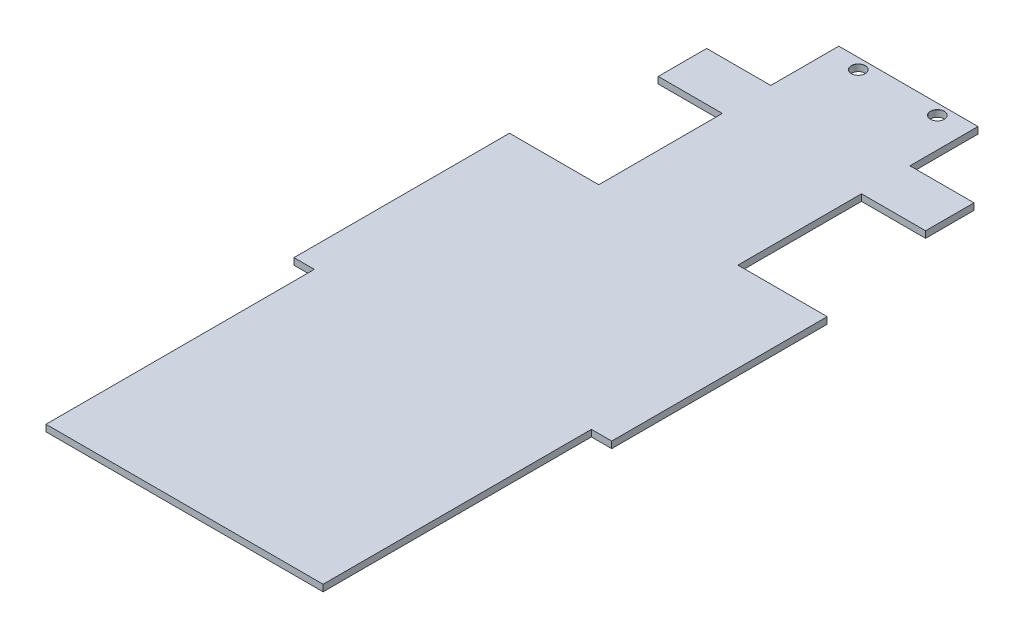
SolidWorks part; units mm, degrees
ref_plane "Plan de face" through (0, 0, 0) normal (0, 0, 1) x (1, 0, 0)
ref_plane "Plan de dessus" through (0, 0, 0) normal (0, 1, 0) x (1, 0, 0)
ref_plane "Plan de droite" through (0, 0, 0) normal (1, 0, 0) x (0, 0, -1)
sketch "Esquisse1" plane through (0, 0, 0) normal (0, 1, 0) x (1, 0, 0)
  line L3 (45, -30.525) -> (45, 30.525)
  line L5 (-45, -30.525) -> (-45, 30.525)
  line L10 (-19.715, 79.245) -> (-19.715, 98.525)
  line L12 (19.715, 98.525) -> (-19.715, 98.525)
  line L15 (-19.715, 65.525) -> (-37.865, 65.525)
  line L16 (-19.715, 79.245) -> (-37.865, 79.245)
  line L17 (-37.865, 79.245) -> (-37.865, 65.525)
  line L18 (19.715, 79.245) -> (37.865, 79.245)
  line L19 (37.865, 79.245) -> (37.865, 65.525)
  line L20 (37.865, 65.525) -> (19.715, 65.525)
  line L21 (-19.715, 65.525) -> (-19.715, 30.525)
  line L22 (19.715, 98.525) -> (19.715, 79.245)
  line L23 (-39.25, -106.525) -> (39.25, -106.525)
  line L24 (-39.25, -106.525) -> (-39.25, -30.525)
  line L25 (39.25, -106.525) -> (39.25, -30.525)
  line L26 (19.715, 65.525) -> (19.715, 30.525)
  line L27 (-45, 30.525) -> (-19.715, 30.525)
  line L28 (19.715, 30.525) -> (45, 30.525)
  line L29 (-45, -30.525) -> (-39.25, -30.525)
  line L30 (39.25, -30.525) -> (45, -30.525)
  dimension "D1" = 39.43
  dimension "D2" = 35
  dimension "D3" = 13.72
  dimension "D4" = 18.15
extrude "Boss.-Extru.6" add sketch "Esquisse1" along normal blind 1.87 contours L5 L27 L21 L15 L17 L16 L10 L12 L22 L18 L19 L20 L26 L28 L3 L30 L25 L23 L24 L29
sketch "Esquisse5" plane through (0, 1.87, 0) normal (0, 1, 0) x (1, 0, 0)
  circle A0 centre (-11.195, 95.525) radius 1.95
  circle A1 centre (11.195, 95.525) radius 1.95
hole_wizard "Dégagement M3.52" positions "Esquisse3D1" profile "Esquisse6" hole size "M3.5" standard "Ansi Metric" end condition through all
sketch3d "Esquisse3D1"
  point P0 (-11.195, 1.87, -95.525)
  point P3 (11.195, 1.87, -95.525)
sketch "Esquisse6" plane through (-11.195, 1.87, -95.525) normal (1, 0, 0) x (0, 0, 1)
  line L0 (0, 0) -> (0, 1.87)
  line L1 (0, 1.87) -> (1.95, 1.87)
  line L2 (1.95, 1.87) -> (1.95, 0.025)
  line L3 (1.95, 0.025) -> (1.975, 0)
  line L5 (1.975, 0) -> (0, 0)
  line L6 (-1.95, 0.025) -> (-1.975, 0) construction
  line L11 (0, -6.35) -> (0, 107.95) construction
  dimension "Diamètre du perçage jusqu'au prochain" = 3.9
  dimension "Profondeur du perçage jusqu'au prochain" = 1.87
  dimension "Diamètre du fraisage entrant" = 3.95
  dimension "Angle du fraisage entrant" = 90
